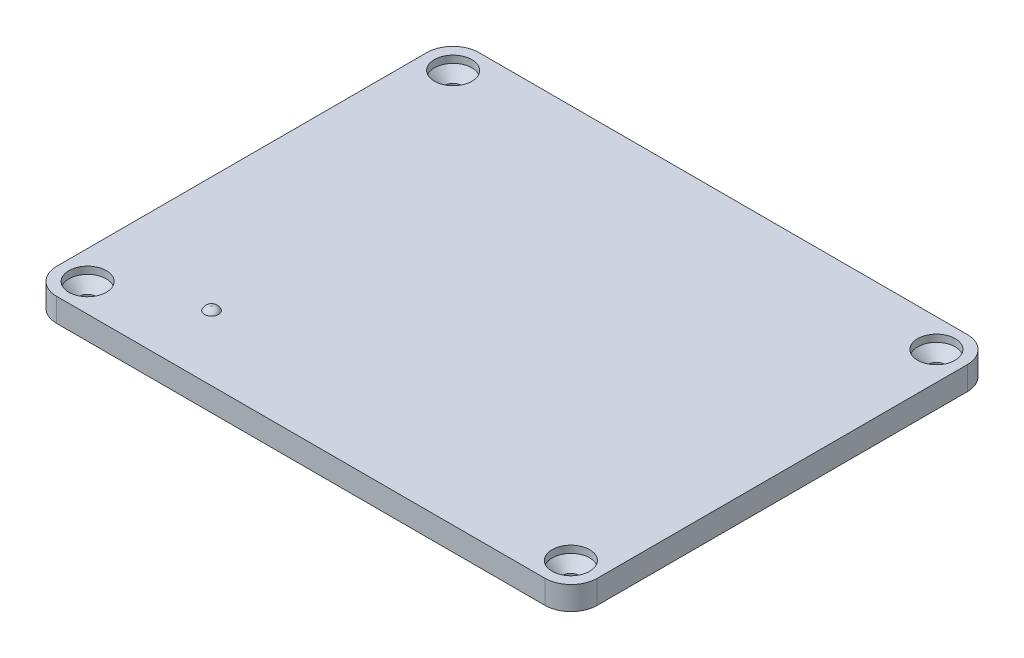
SolidWorks part; units mm, degrees
ref_plane "Front" through (0, 0, 0) normal (0, 0, 1) x (1, 0, 0)
ref_plane "Top" through (0, 0, 0) normal (0, 1, 0) x (1, 0, 0)
ref_plane "Right" through (0, 0, 0) normal (1, 0, 0) x (0, 0, -1)
sketch "Sketch1" plane through (0, 0, 0) normal (0, 1, 0) x (1, 0, 0)
  line L1 (-57.5945, 44.9961) -> (57.5945, 44.9961)
  line L2 (-57.5945, 44.9961) -> (-57.5945, -44.9961)
  line L3 (-57.5945, -44.9961) -> (57.5945, -44.9961)
  line L4 (57.5945, 44.9961) -> (57.5945, -44.9961)
  line L5 (-57.5945, 44.9961) -> (57.5945, -44.9961) construction
  line L6 (-57.5945, -44.9961) -> (57.5945, 44.9961) construction
  point P0 (0, 0)
  dimension "D1" = 89.9922
  dimension "D2" = 115.189
extrude "Boss-Extrude1" add sketch "Sketch1" along normal blind 5.0038
sketch "Sketch2" plane through (0, 0, 0) normal (0, -1, 0) x (1, 0, 0)
  line L0 (-41.8973, 39.8653) -> (41.8973, 39.8653)
  line L1 (-41.8973, -39.8653) -> (41.8973, -39.8653)
  line L2 (52.4637, 29.7561) -> (52.4637, -20.5105)
  line L3 (-52.4637, 20.5105) -> (-52.4637, -29.7561)
  line L4 (-57.5945, 44.9961) -> (57.5945, 44.9961) construction
  line L5 (57.5945, -44.9961) -> (-57.5945, -44.9961) construction
  line L6 (-57.5945, -44.9961) -> (-57.5945, 44.9961) construction
  line L7 (57.5945, 44.9961) -> (57.5945, -44.9961) construction
  line L8 (-51.8287, 21.1455) -> (-51.2445, 21.1455)
  line L9 (-42.5323, 29.8577) -> (-42.5323, 39.2303)
  line L10 (42.5323, 39.2303) -> (42.5323, 38.9509)
  line L11 (51.0921, 30.3911) -> (51.8287, 30.3911)
  line L12 (51.8287, -21.1455) -> (51.2445, -21.1455)
  line L13 (42.5323, -29.8577) -> (42.5323, -39.2303)
  line L14 (-42.5323, -39.2303) -> (-42.5323, -38.9509)
  line L15 (-51.0921, -30.3911) -> (-51.8287, -30.3911)
  arc A0 (-52.4637, -29.7561) -> (-51.8287, -30.3911) centre (-51.8287, -29.7561) ccw
  arc A1 (-42.5323, -39.2303) -> (-41.8973, -39.8653) centre (-41.8973, -39.2303) ccw
  arc A2 (41.8973, -39.8653) -> (42.5323, -39.2303) centre (41.8973, -39.2303) ccw
  arc A3 (51.8287, -21.1455) -> (52.4637, -20.5105) centre (51.8287, -20.5105) ccw
  arc A4 (52.4637, 29.7561) -> (51.8287, 30.3911) centre (51.8287, 29.7561) ccw
  arc A5 (42.5323, 39.2303) -> (41.8973, 39.8653) centre (41.8973, 39.2303) ccw
  arc A6 (-41.8973, 39.8653) -> (-42.5323, 39.2303) centre (-41.8973, 39.2303) ccw
  arc A7 (-51.8287, 21.1455) -> (-52.4637, 20.5105) centre (-51.8287, 20.5105) ccw
  arc A8 (42.5323, -29.8577) -> (51.2445, -21.1455) centre (51.2445, -29.8577) cw
  arc A9 (-42.5323, 29.8577) -> (-51.2445, 21.1455) centre (-51.2445, 29.8577) cw
  arc A10 (-42.5323, -38.9509) -> (-51.0921, -30.3911) centre (-51.0921, -38.9509) ccw
  arc A11 (51.0921, 30.3911) -> (42.5323, 38.9509) centre (51.0921, 38.9509) cw
  dimension "D5" = 0.635
  dimension "D14" = 8.7122
  dimension "D15" = 8.5598
  dimension "D1" = 5.1308
  dimension "D2" = 5.1308
  dimension "D3" = 5.1308
  dimension "D4" = 5.1308
  dimension "D6" = 14.605
  dimension "D7" = 15.0622
  dimension "D8" = 15.0622
  dimension "D9" = 14.605
  dimension "D10" = 23.8506
  dimension "D11" = 23.8506
  dimension "D12" = 15.0622
  dimension "D13" = 15.0622
extrude "Cut-Extrude1" cut sketch "Sketch2" against normal blind 2.54
sketch "Sketch3" plane through (0, 0, 0) normal (0, -1, 0) x (-1, 0, 0)
  line L0 (-57.5945, 44.9961) -> (57.5945, 44.9961) construction
  line L1 (-57.5945, -44.9961) -> (-57.5945, 44.9961) construction
  line L2 (57.5945, 44.9961) -> (57.5945, -44.9961) construction
  line L3 (57.5945, -44.9961) -> (-57.5945, -44.9961) construction
  circle A0 centre (51.4985, -29.8577) radius 3.3655
  circle A1 centre (-51.4985, 29.8577) radius 3.3655
  dimension "D1" = 6.731
  dimension "D2" = 6.731
  dimension "D3" = 15.1384
  dimension "D4" = 6.096
  dimension "D5" = 6.096
  dimension "D6" = 15.1384
extrude "Cut-Extrude2" cut sketch "Sketch3" against normal blind 2.54
fillet "Fillet1" radius 5.5626 4 edges at (-57.5945, 2.5019, -44.9961) (57.5945, 2.5019, -44.9961) (57.5945, 2.5019, 44.9961) (-57.5945, 2.5019, 44.9961)
sketch "Sketch6" plane through (0, 5.0038, 0) normal (0, 1, 0) x (1, 0, 0)
  line L0 (52.0319, 44.9961) -> (-52.0319, 44.9961) construction
  line L1 (-52.0319, -44.9961) -> (52.0319, -44.9961) construction
  line L2 (-57.5945, 39.4335) -> (-57.5945, -39.4335) construction
  line L3 (57.5945, -39.4335) -> (57.5945, 39.4335) construction
  circle A0 centre (-51.4985, 38.9509) radius 4.0005
  circle A1 centre (51.4985, 38.9509) radius 4.0005
  circle A2 centre (51.4985, -38.9509) radius 4.0005
  circle A3 centre (-51.4985, -38.9509) radius 4.0005
  dimension "D1" = 8.001
  dimension "D2" = 8.001
  dimension "D3" = 8.001
  dimension "D4" = 8.001
  dimension "D5" = 6.0452
  dimension "D6" = 6.0452
  dimension "D7" = 6.0452
  dimension "D8" = 6.0452
  dimension "D9" = 6.096
  dimension "D10" = 6.096
  dimension "D11" = 6.096
  dimension "D12" = 6.096
extrude "Cut-Extrude3" cut sketch "Sketch6" against normal blind 1.524
sketch "Sketch7" plane through (0, 0, 0) normal (0, -1, 0) x (1, 0, 0)
  circle A0 centre (51.4985, 38.9509) radius 1.905
  circle A1 centre (51.4985, -38.9509) radius 1.905
  circle A2 centre (-51.4985, -38.9509) radius 1.905
  circle A3 centre (-51.4985, 38.9509) radius 1.905
  dimension "D1" = 3.81
extrude "Cut-Extrude4" cut sketch "Sketch7" against normal blind 1.27
loft "Cut-Loft1" cut section edge at (51.4985, 3.4798, -34.9504) section edge at (51.4985, 1.27, -40.8559) connector at (52.9595, 3.4798, -35.2267) connector at (52.6858, 1.27, -37.4612)
loft "Cut-Loft2" cut section edge at (51.4985, 3.4798, 42.9514) section edge at (51.4985, 1.27, 37.0459) connector at (53.6165, 3.4798, 35.5571) connector at (52.311, 1.27, 37.2278)
loft "Cut-Loft3" cut section edge at (-51.4985, 3.4798, -34.9504) section edge at (-51.4985, 1.27, -40.8559) connector at (-48.5788, 3.4798, -41.6858) connector at (-50.1846, 1.27, -40.3302)
loft "Cut-Loft4" cut section edge at (-51.4985, 3.4798, 42.9514) section edge at (-51.4985, 1.27, 37.0459) connector at (-49.3021, 3.4798, 35.6073) connector at (-50.4116, 1.27, 37.3864)
sketch "Sketch8" plane through (0, 0, 0) normal (0, -1, 0) x (1, 0, 0)
  line L24 (-53.7337, 20.5105) -> (-53.7337, -29.7561)
  line L25 (-51.8287, -31.6611) -> (-51.0921, -31.6611)
  line L26 (-43.8023, -38.9509) -> (-43.8023, -39.2303)
  line L27 (-41.8973, -41.1353) -> (41.8973, -41.1353)
  line L28 (43.8023, -39.2303) -> (43.8023, -29.8577)
  line L29 (51.2445, -22.4155) -> (51.8287, -22.4155)
  line L30 (53.7337, -20.5105) -> (53.7337, 29.7561)
  line L31 (51.8287, 31.6611) -> (51.0921, 31.6611)
  line L32 (43.8023, 38.9509) -> (43.8023, 39.2303)
  line L33 (41.8973, 41.1353) -> (-41.8973, 41.1353)
  line L34 (-43.8023, 39.2303) -> (-43.8023, 29.8577)
  line L35 (-51.2445, 22.4155) -> (-51.8287, 22.4155)
  line L36 (-53.7337, 20.5105) -> (-53.7337, -29.7561)
  line L37 (-51.8287, -31.6611) -> (-51.0921, -31.6611)
  line L38 (-43.8023, -38.9509) -> (-43.8023, -39.2303)
  line L39 (-41.8973, -41.1353) -> (41.8973, -41.1353)
  line L40 (43.8023, -39.2303) -> (43.8023, -29.8577)
  line L41 (51.2445, -22.4155) -> (51.8287, -22.4155)
  line L42 (53.7337, -20.5105) -> (53.7337, 29.7561)
  line L43 (51.8287, 31.6611) -> (51.0921, 31.6611)
  line L44 (43.8023, 38.9509) -> (43.8023, 39.2303)
  line L45 (41.8973, 41.1353) -> (-41.8973, 41.1353)
  line L46 (-43.8023, 39.2303) -> (-43.8023, 29.8577)
  line L47 (-51.2445, 22.4155) -> (-51.8287, 22.4155)
  line L60 (-56.2737, 20.5105) -> (-56.2737, -29.7561)
  line L61 (-51.8287, -34.2011) -> (-51.0921, -34.2011)
  line L62 (-46.3423, -38.9509) -> (-46.3423, -39.2303)
  line L63 (-41.8973, -43.6753) -> (41.8973, -43.6753)
  line L64 (46.3423, -39.2303) -> (46.3423, -29.8577)
  line L65 (51.2445, -24.9555) -> (51.8287, -24.9555)
  line L66 (56.2737, -20.5105) -> (56.2737, 29.7561)
  line L67 (51.8287, 34.2011) -> (51.0921, 34.2011)
  line L68 (46.3423, 38.9509) -> (46.3423, 39.2303)
  line L69 (41.8973, 43.6753) -> (-41.8973, 43.6753)
  line L70 (-46.3423, 39.2303) -> (-46.3423, 29.8577)
  line L71 (-51.2445, 24.9555) -> (-51.8287, 24.9555)
  line L72 (-56.2737, 20.5105) -> (-56.2737, -29.7561)
  line L73 (-51.8287, -34.2011) -> (-51.0921, -34.2011)
  line L74 (-46.3423, -38.9509) -> (-46.3423, -39.2303)
  line L75 (-41.8973, -43.6753) -> (41.8973, -43.6753)
  line L76 (46.3423, -39.2303) -> (46.3423, -29.8577)
  line L77 (51.2445, -24.9555) -> (51.8287, -24.9555)
  line L78 (56.2737, -20.5105) -> (56.2737, 29.7561)
  line L79 (51.8287, 34.2011) -> (51.0921, 34.2011)
  line L80 (46.3423, 38.9509) -> (46.3423, 39.2303)
  line L81 (41.8973, 43.6753) -> (-41.8973, 43.6753)
  line L82 (-46.3423, 39.2303) -> (-46.3423, 29.8577)
  line L83 (-51.2445, 24.9555) -> (-51.8287, 24.9555)
  arc A24 (-53.7337, -29.7561) -> (-51.8287, -31.6611) centre (-51.8287, -29.7561) ccw
  arc A25 (-43.8023, -38.9509) -> (-51.0921, -31.6611) centre (-51.0921, -38.9509) ccw
  arc A26 (-43.8023, -39.2303) -> (-41.8973, -41.1353) centre (-41.8973, -39.2303) ccw
  arc A27 (41.8973, -41.1353) -> (43.8023, -39.2303) centre (41.8973, -39.2303) ccw
  arc A28 (51.2445, -22.4155) -> (43.8023, -29.8577) centre (51.2445, -29.8577) ccw
  arc A29 (51.8287, -22.4155) -> (53.7337, -20.5105) centre (51.8287, -20.5105) ccw
  arc A30 (53.7337, 29.7561) -> (51.8287, 31.6611) centre (51.8287, 29.7561) ccw
  arc A31 (43.8023, 38.9509) -> (51.0921, 31.6611) centre (51.0921, 38.9509) ccw
  arc A32 (43.8023, 39.2303) -> (41.8973, 41.1353) centre (41.8973, 39.2303) ccw
  arc A33 (-41.8973, 41.1353) -> (-43.8023, 39.2303) centre (-41.8973, 39.2303) ccw
  arc A34 (-51.2445, 22.4155) -> (-43.8023, 29.8577) centre (-51.2445, 29.8577) ccw
  arc A35 (-51.8287, 22.4155) -> (-53.7337, 20.5105) centre (-51.8287, 20.5105) ccw
  arc A36 (-53.7337, -29.7561) -> (-51.8287, -31.6611) centre (-51.8287, -29.7561) ccw
  arc A37 (-43.8023, -38.9509) -> (-51.0921, -31.6611) centre (-51.0921, -38.9509) ccw
  arc A38 (-43.8023, -39.2303) -> (-41.8973, -41.1353) centre (-41.8973, -39.2303) ccw
  arc A39 (41.8973, -41.1353) -> (43.8023, -39.2303) centre (41.8973, -39.2303) ccw
  arc A40 (51.2445, -22.4155) -> (43.8023, -29.8577) centre (51.2445, -29.8577) ccw
  arc A41 (51.8287, -22.4155) -> (53.7337, -20.5105) centre (51.8287, -20.5105) ccw
  arc A42 (53.7337, 29.7561) -> (51.8287, 31.6611) centre (51.8287, 29.7561) ccw
  arc A43 (43.8023, 38.9509) -> (51.0921, 31.6611) centre (51.0921, 38.9509) ccw
  arc A44 (43.8023, 39.2303) -> (41.8973, 41.1353) centre (41.8973, 39.2303) ccw
  arc A45 (-41.8973, 41.1353) -> (-43.8023, 39.2303) centre (-41.8973, 39.2303) ccw
  arc A46 (-51.2445, 22.4155) -> (-43.8023, 29.8577) centre (-51.2445, 29.8577) ccw
  arc A47 (-51.8287, 22.4155) -> (-53.7337, 20.5105) centre (-51.8287, 20.5105) ccw
  arc A60 (-56.2737, -29.7561) -> (-51.8287, -34.2011) centre (-51.8287, -29.7561) ccw
  arc A61 (-46.3423, -38.9509) -> (-51.0921, -34.2011) centre (-51.0921, -38.9509) ccw
  arc A62 (-46.3423, -39.2303) -> (-41.8973, -43.6753) centre (-41.8973, -39.2303) ccw
  arc A63 (41.8973, -43.6753) -> (46.3423, -39.2303) centre (41.8973, -39.2303) ccw
  arc A64 (51.2445, -24.9555) -> (46.3423, -29.8577) centre (51.2445, -29.8577) ccw
  arc A65 (51.8287, -24.9555) -> (56.2737, -20.5105) centre (51.8287, -20.5105) ccw
  arc A66 (56.2737, 29.7561) -> (51.8287, 34.2011) centre (51.8287, 29.7561) ccw
  arc A67 (46.3423, 38.9509) -> (51.0921, 34.2011) centre (51.0921, 38.9509) ccw
  arc A68 (46.3423, 39.2303) -> (41.8973, 43.6753) centre (41.8973, 39.2303) ccw
  arc A69 (-41.8973, 43.6753) -> (-46.3423, 39.2303) centre (-41.8973, 39.2303) ccw
  arc A70 (-51.2445, 24.9555) -> (-46.3423, 29.8577) centre (-51.2445, 29.8577) ccw
  arc A71 (-51.8287, 24.9555) -> (-56.2737, 20.5105) centre (-51.8287, 20.5105) ccw
  arc A72 (-56.2737, -29.7561) -> (-51.8287, -34.2011) centre (-51.8287, -29.7561) ccw
  arc A73 (-46.3423, -38.9509) -> (-51.0921, -34.2011) centre (-51.0921, -38.9509) ccw
  arc A74 (-46.3423, -39.2303) -> (-41.8973, -43.6753) centre (-41.8973, -39.2303) ccw
  arc A75 (41.8973, -43.6753) -> (46.3423, -39.2303) centre (41.8973, -39.2303) ccw
  arc A76 (51.2445, -24.9555) -> (46.3423, -29.8577) centre (51.2445, -29.8577) ccw
  arc A77 (51.8287, -24.9555) -> (56.2737, -20.5105) centre (51.8287, -20.5105) ccw
  arc A78 (56.2737, 29.7561) -> (51.8287, 34.2011) centre (51.8287, 29.7561) ccw
  arc A79 (46.3423, 38.9509) -> (51.0921, 34.2011) centre (51.0921, 38.9509) ccw
  arc A80 (46.3423, 39.2303) -> (41.8973, 43.6753) centre (41.8973, 39.2303) ccw
  arc A81 (-41.8973, 43.6753) -> (-46.3423, 39.2303) centre (-41.8973, 39.2303) ccw
  arc A82 (-51.2445, 24.9555) -> (-46.3423, 29.8577) centre (-51.2445, 29.8577) ccw
  arc A83 (-51.8287, 24.9555) -> (-56.2737, 20.5105) centre (-51.8287, 20.5105) ccw
  dimension "D1" = 1.27
  dimension "D2" = 3.81
extrude "Cut-Extrude5" cut sketch "Sketch8" against normal blind 2.54
sketch "Sketch9" plane through (0, 5.0038, 0) normal (0, 1, 0) x (1, 0, 0)
  line L0 (-52.0319, -44.9961) -> (52.0319, -44.9961) construction
  line L1 (-57.5945, 39.4335) -> (-57.5945, -39.4335) construction
  circle A0 centre (-32.9311, -31.1023) radius 1.4859
  dimension "D1" = 2.9718
  dimension "D2" = 13.8938
  dimension "D3" = 24.6634
extrude "Cut-Extrude6" cut sketch "Sketch9" against normal through all
ref_plane "Plane1" through (0, 1.778, 0) normal (0, -1, 0) x (-1, 0, 0)
sketch "Sketch11" plane through (0, 1.778, 0) normal (0, -1, 0) x (-1, 0, 0)
  circle A0 centre (32.9311, -31.1023) radius 2.032
  dimension "D1" = 4.064
extrude "Boss-Extrude2" add sketch "Sketch11" against normal up to surface (0.762 mm away) separate body up to face at (-32.9311, 2.54, 29.6164)
sketch "Sketch13" plane through (0, 2.54, 0) normal (0, 1, 0) x (1, 0, 0)
  circle A0 centre (-32.9311, -31.1023) radius 1.4859
  dimension "D1" = 2.9718
extrude "Boss-Extrude3" add sketch "Sketch13" along normal blind 3.302
fillet "Fillet2" radius 1.4859 1 edges at (-32.9311, 5.842, 32.5882)
